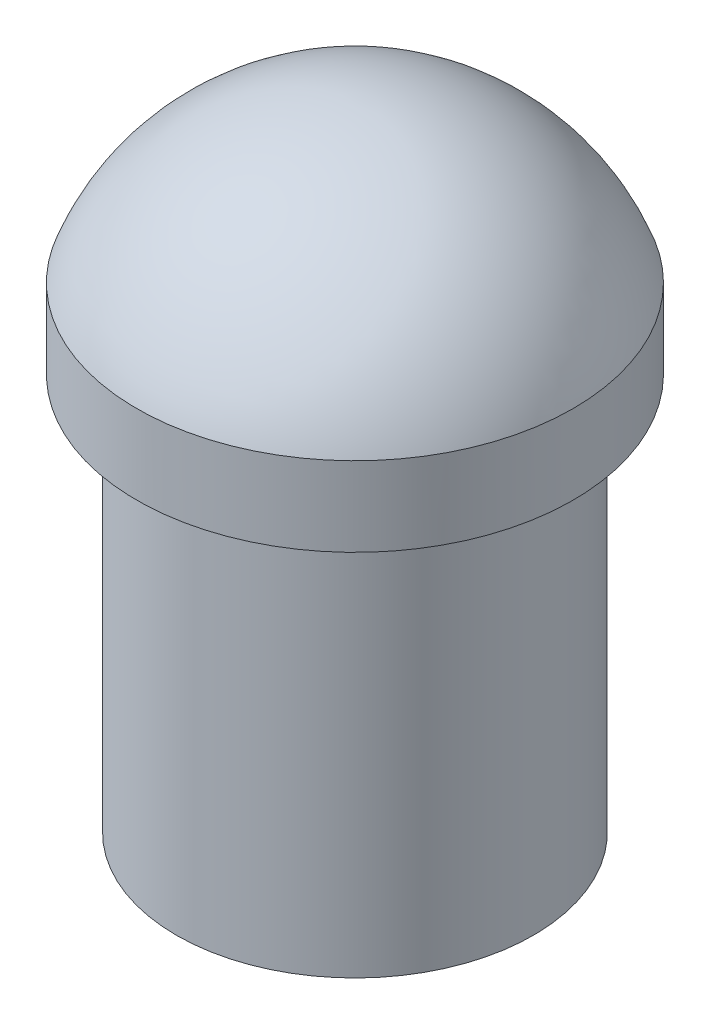
SolidWorks part; units mm, degrees
ref_plane "Front Plane" through (0, 0, 0) normal (0, 0, 1) x (1, 0, 0)
ref_plane "Top Plane" through (0, 0, 0) normal (0, 1, 0) x (1, 0, 0)
ref_plane "Right Plane" through (0, 0, 0) normal (1, 0, 0) x (0, 0, -1)
sketch "Sketch1" plane through (0, 0, 0) normal (0, 1, 0) x (1, 0, 0)
  circle A0 centre (0, 0) radius 2.25
  dimension "D1" = 4.5
extrude "Boss-Extrude1" add sketch "Sketch1" along normal blind 5
sketch "Sketch2" plane through (0, 0, 0) normal (0, 0, 1) x (1, 0, 0)
  line L0 (0, -2.0405) -> (0, 1.0153) construction
  line L1 (2.25, 5) -> (-2.25, 5) construction
  line L3 (-2.75, 6) -> (-2.75, 5)
  line L4 (-2.75, 5) -> (0, 5)
  line L7 (-2.75, 5) -> (0, 5) construction
  line L8 (0, 7.9262) -> (0, 5)
  arc A0 (0, 7.9262) -> (-2.75, 6) centre (0, 5) ccw
  point P7 (0, 5)
  point P8 (0, 4.7249)
  point P11 (0, 4.7114)
  dimension "D1" = 1
  dimension "D2" = 5.5
revolve "Revolve1" add sketch "Sketch2" angle 360 about L0
